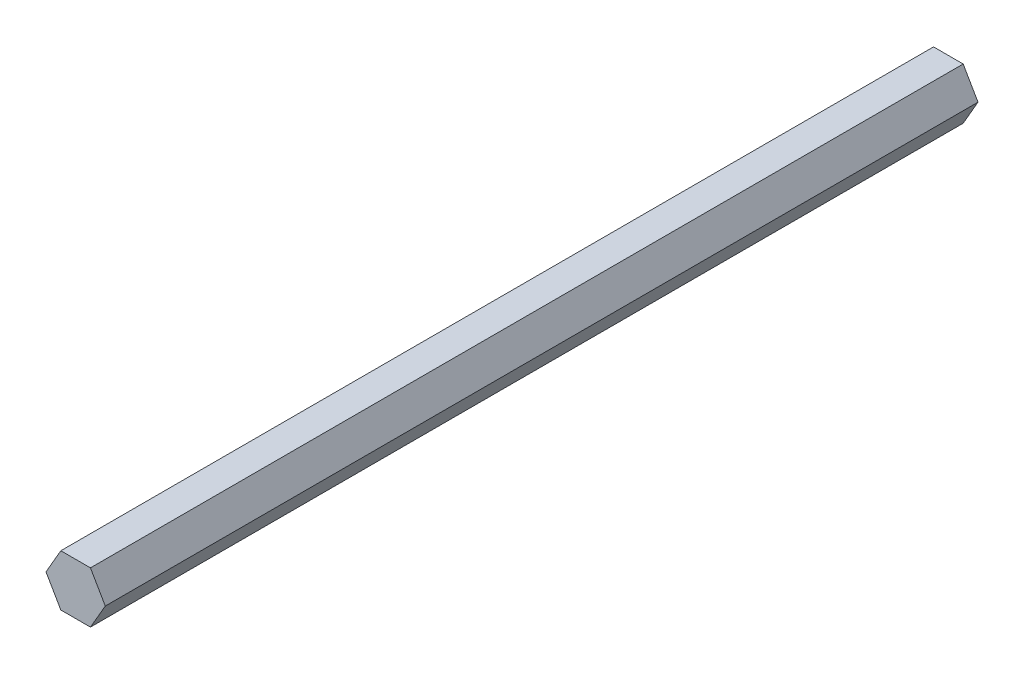
SolidWorks part; units mm, degrees
ref_plane "Front Plane" through (0, 0, 0) normal (0, 0, 1) x (1, 0, 0)
ref_plane "Top Plane" through (0, 0, 0) normal (0, 1, 0) x (1, 0, 0)
ref_plane "Right Plane" through (0, 0, 0) normal (1, 0, 0) x (0, 0, -1)
sketch "Sketch1" plane through (0, 0, 0) normal (0, 0, 1) x (1, 0, 0)
  line L1 (-7.3323, 0) -> (-3.6662, -6.35)
  line L2 (-3.6662, -6.35) -> (3.6662, -6.35)
  line L3 (3.6662, -6.35) -> (7.3323, 0)
  line L4 (7.3323, 0) -> (3.6662, 6.35)
  line L5 (3.6662, 6.35) -> (-3.6662, 6.35)
  line L6 (-3.6662, 6.35) -> (-7.3323, 0)
  circle A0 centre (0, 0) radius 6.35 construction
  dimension "D1" = 12.7
extrude "Boss-Extrude1" add sketch "Sketch1" along normal blind 215.9
ref_axis "Axis1" through (0, 0, -5.5399) along (0, 0, 1)
